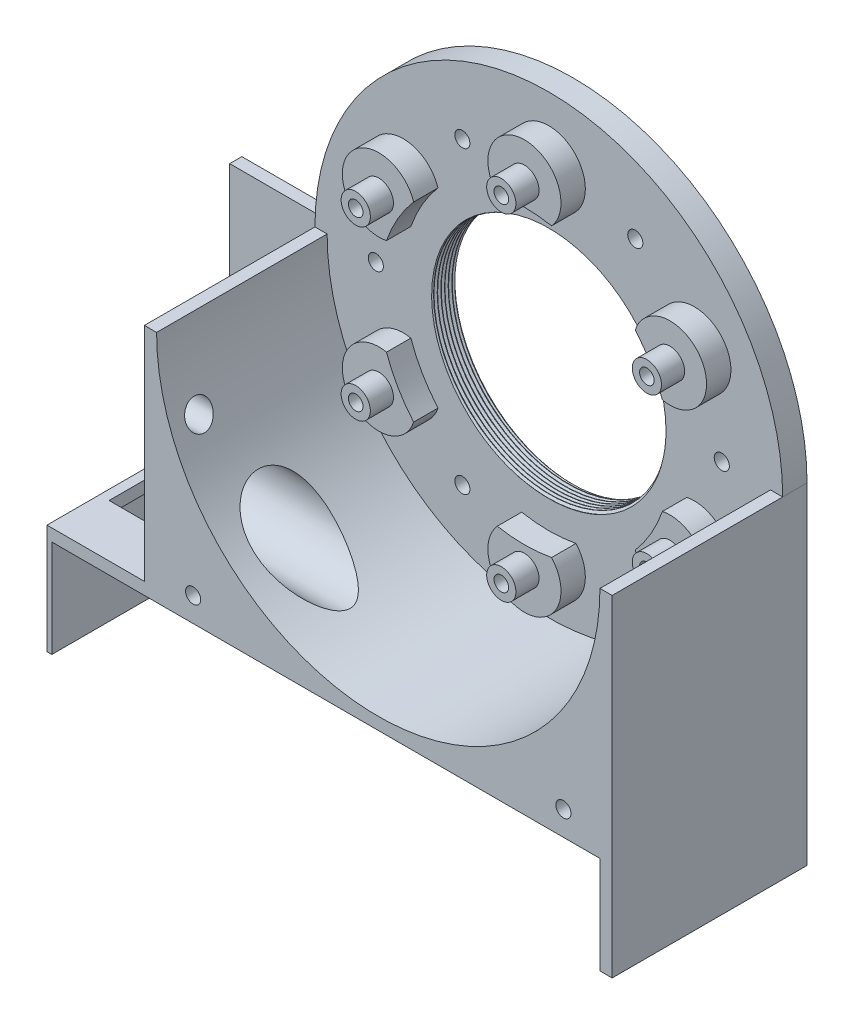
SolidWorks part; units mm, degrees
ref_plane "Plan de face" through (0, 0, 0) normal (0, 0, 1) x (1, 0, 0)
ref_plane "Plan de dessus" through (0, 0, 0) normal (0, 1, 0) x (1, 0, 0)
ref_plane "Plan de droite" through (0, 0, 0) normal (1, 0, 0) x (0, 0, -1)
sketch "Esquisse1" plane through (0, 0, 0) normal (0, 0, 1) x (1, 0, 0)
  circle A0 centre (0, 0) radius 23.8
  circle A1 centre (0, 0) radius 48
  dimension "D1" = 47.6
  dimension "D2" = 96
extrude "Boss.-Extru.1" add sketch "Esquisse1" along normal blind 40
sketch "Esquisse2" plane through (0, 0, 40) normal (0, 0, 1) x (1, 0, 0)
  circle A0 centre (0, 0) radius 45.5
  circle A1 centre (0, 0) radius 48 construction
  dimension "D1" = 2.5
extrude "Enlèv. mat.-Extru.1" cut sketch "Esquisse2" against normal blind 35
sketch "Esquisse3" plane through (0, 0, 5) normal (0, 0, 1) x (1, 0, 0)
  circle A0 centre (0, 34.5) radius 7.5
  circle A3 centre (29.8779, 17.25) radius 7.5
  circle A4 centre (29.8779, -17.25) radius 7.5
  circle A5 centre (0, -34.5) radius 7.5
  circle A6 centre (-29.8779, -17.25) radius 7.5
  circle A7 centre (-29.8779, 17.25) radius 7.5
  dimension "D1" = 15
  dimension "D2" = 34.5
  dimension "D3" = 6
extrude "Boss.-Extru.2" add sketch "Esquisse3" along normal blind 5
sketch "Esquisse4" plane through (0, 0, 5) normal (0, 0, 1) x (1, 0, 0)
  circle A0 centre (0, 0) radius 30
  dimension "D1" = 60
extrude "Enlèv. mat.-Extru.2" cut sketch "Esquisse4" along normal blind 29
sketch "Esquisse13" plane through (0, 0, 10) normal (0, 0, 1) x (1, 0, 0)
  circle A0 centre (0, 34.5) radius 3
  circle A1 centre (0, 34.5) radius 1.5
  circle A2 centre (29.8779, 17.25) radius 3
  circle A3 centre (29.8779, 17.25) radius 1.5
  circle A4 centre (29.8779, -17.25) radius 3
  circle A5 centre (29.8779, -17.25) radius 1.5
  circle A6 centre (0, -34.5) radius 3
  circle A7 centre (0, -34.5) radius 1.5
  circle A8 centre (-29.8779, -17.25) radius 3
  circle A9 centre (-29.8779, -17.25) radius 1.5
  circle A10 centre (-29.8779, 17.25) radius 3
  circle A11 centre (-29.8779, 17.25) radius 1.5
  dimension "D1" = 6
  dimension "D2" = 3
  dimension "D3" = 6
extrude "Boss.-Extru.4" add sketch "Esquisse13" along normal blind 4.75
chamfer "Chanfrein2" distance 0.5 angle 45 1 edges at (23.8, 0, 0)
sketch "Esquisse14" plane through (0, 0, 0) normal (0, 0, 1) x (1, 0, 0)
  circle A0 centre (0, 0) radius 24.5
curve "Hélice/Spirale1" pitch 0.75 height 7.5 turns 10
sketch "Esquisse15" plane through (0, 0, 0) normal (-1, 0, 0) x (0, 0, 1)
  line L4 (0.501, -22.0731) -> (0.501, -22.5925) construction
  line L9 (0.8323, -23.8) -> (0.1698, -23.8)
  line L10 (0.1698, -23.8) -> (0.4573, -24.298)
  line L11 (0.4573, -24.298) -> (0.5448, -24.298)
  line L12 (0.8323, -23.8) -> (0.5448, -24.298)
  point P7 (0.501, -24.298)
  point P8 (0.501, -23.8)
  dimension "D1" = 60
  dimension "D2" = 0.0875
  dimension "D3" = 23.8
  dimension "D6" = 0.6625
sweep "Enlèvement de matière-Balayage1" cut profiles "Esquisse15" path "Hélice/Spirale1"
sketch "Esquisse23" plane through (0, 0, 40) normal (0, 0, 1) x (1, 0, 0)
  line L0 (-43.942, 0) -> (-49.526, 0)
  line L2 (43.942, 0) -> (49.526, 0)
  arc A0 (49.526, 0) -> (-49.526, 0) centre (0, 0) ccw
  arc A1 (43.942, 0) -> (-43.942, 0) centre (0, 0) ccw
extrude "Enlèv. mat.-Extru.6" cut sketch "Esquisse23" against normal up to surface (35 mm away) up to face at (-0.0839, -0.1997, 5)
sketch "Esquisse27" plane through (0, 0, 0) normal (1, 0, 0) x (0, 0, -1)
  circle A0 centre (-27.5, -34) radius 7.675
  dimension "D1" = 27.5
  dimension "D3" = 15.35
  dimension "D2" = 34
extrude "Enlèv. mat.-Extru.7" cut sketch "Esquisse27" against normal through all
sketch3d "Esquisse3D2" plane through (0, 0, 0) normal (0, 0, 1) x (1, 0, 0)
  dimension "D1" = 48
sketch "Esquisse31" plane through (0, 0, 5) normal (0, 0, 1) x (1, 0, 0)
  line L0 (0, 0) -> (-55.0987, -0.0031) construction
  line L1 (0, 0) -> (-30.9754, 53.644) construction
  circle A0 centre (-17.7517, 30.7429) radius 1.55
  circle A2 centre (17.7483, 30.7449) radius 1.55
  circle A3 centre (35.5, 0.002) radius 1.55
  circle A4 centre (17.7517, -30.7429) radius 1.55
  circle A5 centre (-17.7483, -30.7449) radius 1.55
  circle A6 centre (-35.5, -0.002) radius 1.55
  point P5 (-48, 0)
  point P8 (-55.0987, -0.002)
  dimension "D1" = 3.1
  dimension "D2" = 60
  dimension "D3" = 35.5
  dimension "D4" = 6
extrude "Enlèv. mat.-Extru.8" cut sketch "Esquisse31" against normal through all
sketch "Esquisse33" plane through (-48, 0, 0) normal (1, 0, 0) x (0, 0, -1)
  line L0 (-24.2366, -37.2634) -> (-32.0205, -29.4795) construction
  line L1 (13.3219, -63.5082) -> (-63.8041, 13.6179) construction
  line L2 (-27.5, -34) -> (-32.3825, -38.8825) construction
  line L3 (-40, -48) -> (-40, 9.0935) construction
  line L5 (-40, -48) -> (0, -48)
  line L6 (-40, -48) -> (-40, 0)
  line L7 (-40, 0) -> (0, 0)
  line L8 (0, -48) -> (0, 0)
  circle A0 centre (-27.5, -34) radius 7.675
  circle A1 centre (-34.2175, -15.9688) radius 2.75
  circle A2 centre (-9.4688, -40.7175) radius 2.75
  dimension "D1" = 8
  dimension "D2" = 5.5
  dimension "D3" = 17.5
  dimension "D5" = 45
extrude "Boss.-Extru.5" add sketch "Esquisse33" along normal up to next
sketch "Esquisse35" plane through (-48, 0, 0) normal (-1, 0, 0) x (0, 0, 1)
  circle A0 centre (34.2175, -15.9688) radius 2.75
  circle A1 centre (9.4688, -40.7175) radius 2.75
extrude "Enlèv. mat.-Extru.12" cut sketch "Esquisse35" against normal blind 16
sketch "Esquisse36" plane through (-48, 0, 0) normal (-1, 0, 0) x (0, 0, 1)
  line L0 (2.5, 0) -> (0, 0)
  line L1 (0, 0) -> (5, 0) construction
  line L2 (0, 0) -> (0, -48)
  line L3 (0, -48) -> (0, 0) construction
  line L4 (0, -48) -> (40, -48)
  line L5 (40, -48) -> (0, -48) construction
  line L6 (40, -48) -> (40, -45.5)
  line L7 (40, -45.5) -> (2.5, -45.5)
  line L8 (2.5, -45.5) -> (2.5, 0)
  dimension "D1" = 2.5
extrude "Boss.-Extru.6" add sketch "Esquisse36" along normal blind 20
sketch "Esquisse37" plane through (0, -48, 0) normal (0, -1, 0) x (1, 0, 0)
  line L0 (0, 0) -> (0, 40) construction
  line L1 (-68, 0) -> (0, 0)
  line L2 (-68, 0) -> (-68, 2.5)
  line L3 (-68, 2.5) -> (0, 2.5)
  line L4 (0, 0) -> (0, 2.5)
  dimension "D1" = 2.5
extrude "Boss.-Extru.7" add sketch "Esquisse37" along normal blind 20
sketch "Esquisse39" plane through (0, -48, 0) normal (0, -1, 0) x (1, 0, 0)
  line L0 (0, 2.5) -> (-68, 2.5) construction
  line L1 (-68, 40) -> (-67, 40)
  line L2 (-68, 40) -> (-68, 2.5)
  line L3 (-68, 2.5) -> (-67, 2.5)
  line L4 (-67, 40) -> (-67, 2.5)
  dimension "D1" = 1
extrude "Boss.-Extru.8" add sketch "Esquisse39" along normal up to surface (20 mm away) up to face at (-34, -68, 1.25)
sketch "Esquisse38" plane through (0, -48, 0) normal (0, -1, 0) x (1, 0, 0)
  line L0 (-73.0785, 21.25) -> (7.2876, 21.25) construction
  line L1 (0, 2.5) -> (-67, 2.5) construction
  line L2 (-22, 50.4468) -> (-22, -9.1322) construction
  line L3 (-67, 2.5) -> (-67, 40) construction
  line L4 (-12, 49.0594) -> (-12, -16.4066) construction
  line L5 (20, 49.0594) -> (20, -14.6957) construction
  dimension "D1" = 18.75
  dimension "D2" = 45
  dimension "D3" = 32
  dimension "D4" = 10
sketch "Esquisse40" plane through (0, -48, 0) normal (0, -1, 0) x (1, 0, 0)
  line L0 (-73.0785, 21.25) -> (7.2876, 21.25) construction
  line L1 (-66, 29.25) -> (-58, 29.25)
  line L2 (-66, 29.25) -> (-66, 13.25)
  line L3 (-66, 13.25) -> (-58, 13.25)
  line L4 (-58, 29.25) -> (-58, 13.25)
  line L5 (-66, 29.25) -> (-58, 13.25) construction
  line L6 (-66, 13.25) -> (-58, 29.25) construction
  line L7 (-67, 2.5) -> (-67, 40) construction
  point P0 (-62, 21.25)
  dimension "D1" = 16
  dimension "D2" = 8
  dimension "D3" = 1
extrude "Enlèv. mat.-Extru.13" cut sketch "Esquisse40" against normal blind 13
sketch "Esquisse43" plane through (0, 0, 40) normal (0, 0, 1) x (1, 0, 0)
  line L0 (0, -45.5) -> (0, -48)
  line L1 (45.5, 0) -> (48, 0)
  line L2 (48, 0) -> (48, -48)
  line L4 (0, -48) -> (48, -48)
  arc A0 (-45.5, 0) -> (45.5, 0) centre (0, 0) ccw construction
  arc A1 (0, -45.5) -> (45.5, 0) centre (0, 0) ccw
extrude "Boss.-Extru.10" add sketch "Esquisse43" against normal up to surface (40 mm away) up to face at (-33.95, -0.002, 0)
sketch "Esquisse45" plane through (0, -48, 0) normal (0, -1, 0) x (1, 0, 0)
  line L0 (48, 0) -> (48, 40) construction
  line L1 (0, 0) -> (48, 0)
  line L2 (0, 0) -> (0, 2.5)
  line L3 (0, 2.5) -> (45.5, 2.5)
  line L4 (48, 0) -> (48, 2.5)
  line L5 (48, 40) -> (-67, 40) construction
  line L7 (48, 2.5) -> (48, 40)
  line L8 (48, 40) -> (45.5, 40)
  line L9 (45.5, 2.5) -> (45.5, 40)
  dimension "D1" = 2.5
extrude "Boss.-Extru.11" add sketch "Esquisse45" along normal up to surface (20 mm away) up to face at (-45, -68, 14.1667)
sketch "Esquisse46" plane through (0, 0, 40) normal (0, 0, 1) x (1, 0, 0)
  line L0 (-58.2365, -43) -> (69.7757, -43) construction
  line L1 (45.5, -48) -> (-67, -48) construction
  line L2 (-48, -45.5) -> (-48, 0) construction
  line L3 (48, -68) -> (48, 0) construction
  circle A0 centre (-38, -43) radius 1.55
  circle A1 centre (38, -43) radius 1.55
  dimension "D2" = 3.1
  dimension "D3" = 10
  dimension "D4" = 3.1
  dimension "D5" = 10
  dimension "D1" = 5
extrude "Enlèv. mat.-Extru.14" cut sketch "Esquisse46" against normal blind 5
